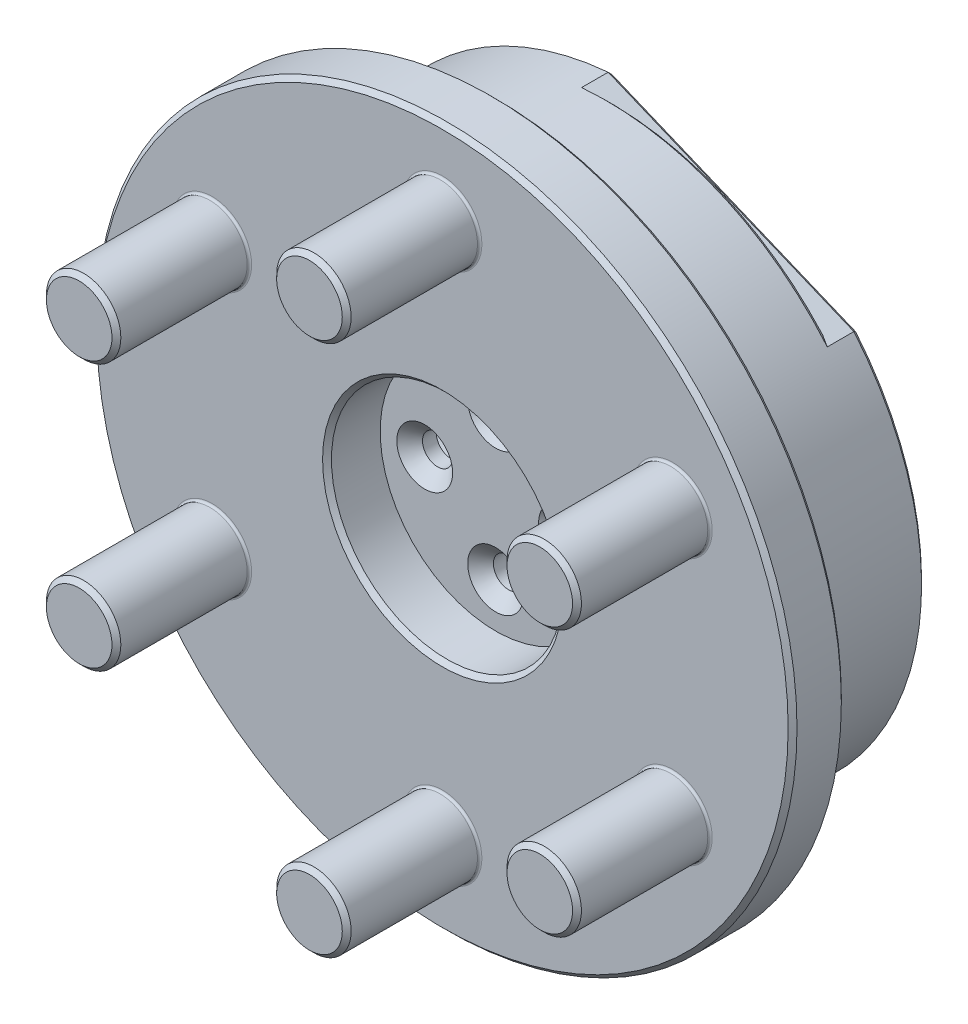
SolidWorks part; units mm, degrees
material "7075-T6, Plate (SS)"
ref_plane "Front Plane" through (0, 0, 0) normal (0, 0, 1) x (1, 0, 0)
ref_plane "Top Plane" through (0, 0, 0) normal (0, 1, 0) x (1, 0, 0)
ref_plane "Right Plane" through (0, 0, 0) normal (1, 0, 0) x (0, 0, -1)
sketch "Sketch1" plane through (0, 0, 0) normal (0, 0, 1) x (1, 0, 0)
  circle A0 centre (0, 0) radius 39.5
  circle A1 centre (0, 30) radius 4.2
  circle A2 centre (0, 0) radius 13.025
  circle A3 centre (25.9808, 15) radius 4.2
  circle A4 centre (25.9808, -15) radius 4.2
  circle A5 centre (0, -30) radius 4.2
  circle A6 centre (-25.9808, -15) radius 4.2
  circle A7 centre (-25.9808, 15) radius 4.2
  point P18 (0, 0)
  dimension "D1" = 79
  dimension "D3" = 8.4
  dimension "D4" = 26.05
  dimension "D2" = 30
  dimension "D5" = 6
extrude "Boss-Extrude1" add sketch "Sketch1" against normal blind 6 contours A0 | A2
extrude "Boss-Extrude2" add sketch "Sketch1<3>" along normal blind 15 contours A3 | A4 | A5 | A6 | A7 | A1 region at (25.9808, 15, 0) region at (25.9808, -15, 0) region at (0, -30, 0) region at (-25.9808, -15, 0) region at (-25.9808, 15, 0)
sketch "Sketch1<3>" plane through (0, 0, 0) normal (0, 0, 1) x (1, 0, 0) same geometry as "Sketch1"
sketch "Sketch2" plane through (0, 0, -6) normal (0, 0, -1) x (-1, 0, 0)
  circle A0 centre (0, 0) radius 32.55
  circle A1 centre (0, 0) radius 17.5
  circle A4 centre (0, 0) radius 25 construction
  point P18 (0, 0)
  dimension "D1" = 65.1
  dimension "D2" = 50
  dimension "D3" = 35
extrude "Boss-Extrude3" add sketch "Sketch2" along normal blind 16 contours A0
sketch "Sketch3" plane through (0, 0, -22) normal (0, 0, -1) x (-1, 0, 0)
  circle A0 centre (0, 0) radius 25 construction
  point P3 (0, 25)
  point P7 (17.6777, 17.6777)
  point P8 (25, 0)
  point P9 (17.6777, -17.6777)
  point P10 (0, -25)
  point P11 (-17.6777, -17.6777)
  point P12 (-25, 0)
  point P13 (-17.6777, 17.6777)
  point P14 (0, 0)
  point P17 (0, 0)
  dimension "D1" = 50
  dimension "D2" = 8
sketch "Sketch5" plane through (0, 0, 0) normal (0, 0, 1) x (1, 0, 0)
  circle A0 centre (0, 30) radius 4
  circle A1 centre (25.9808, 15) radius 4
  circle A2 centre (25.9808, -15) radius 4
  circle A3 centre (0, -30) radius 4
  circle A4 centre (-25.9808, -15) radius 4
  circle A5 centre (-25.9808, 15) radius 4
  point P15 (0, 0)
  dimension "D2" = 8
  dimension "D1" = 30
  dimension "D3" = 6
extrude "Boss-Extrude4" [suppressed] add sketch "Sketch5" along normal blind 15
fillet "Fillet1" [suppressed] radius 0.5
hole_wizard "M5 Tapped Hole1" positions "Sketch6" profile "Sketch7" tap size "M5" standard "ISO"
sketch "Sketch6" plane through (0, 0, -22) normal (0, 0, -1) x (-1, 0, 0)
  point P0 (0, 25)
  point P3 (-17.6777, 17.6777)
  point P6 (-25, 0)
  point P9 (17.6777, 17.6777)
  point P12 (25, 0)
  point P15 (-17.6777, -17.6777)
  point P18 (0, -25)
  point P21 (17.6777, -17.6777)
sketch "Sketch7" plane through (0, 25, -22) normal (1, 0, 0) x (0, 1, 0)
  line L0 (0, 0) -> (0, 8.2618)
  line L1 (0, 8.2618) -> (2.1, 7)
  line L2 (2.1, 7) -> (2.1, 0.425)
  line L3 (2.1, 0.425) -> (2.525, 0)
  line L5 (2.525, 0) -> (0, 0)
  line L6 (-2.1, 0.425) -> (-2.525, 0) construction
  line L10 (0, 8.2618) -> (-2.1, 7) construction
  line L11 (0, -6.35) -> (0, 107.95) construction
  dimension "Tap Drill Dia." = 4.2
  dimension "Tap Drill Depth" = 7
  dimension "Near C'Sink Dia." = 5.05
  dimension "Near C'Sink Angle" = 90
  dimension "Drill Angle" = 118
sketch "Sketch9" plane through (0, 0, -22) normal (0, 0, -1) x (-1, 0, 0)
  line L0 (0, 0) -> (-12.4563, 30.0723) construction
  line L1 (-24.9131, 20.9486) -> (2.8033, 32.4291)
  line L2 (0, 0) -> (0, 32.55) construction
  line L3 (24.9131, -20.9486) -> (-2.8033, -32.4291)
  circle A0 centre (0, 0) radius 32.55 construction
  arc A1 (2.8033, 32.4291) -> (-24.9131, 20.9486) centre (0, 0) ccw
  arc A2 (-12.9309, 13.2303) -> (-13.2303, 12.9309) centre (0, 0) ccw
  arc A3 (-2.8033, -32.4291) -> (24.9131, -20.9486) centre (0, 0) ccw
  circle A4 centre (0, 0) radius 25 construction
  arc A5 (-3.0239, 20.3657) -> (-12.2625, 16.5389) centre (-7.6537, 18.4776) ccw
  arc A6 (12.2625, 16.5389) -> (3.0239, 20.3657) centre (7.6537, 18.4776) ccw
  arc A7 (20.3657, 3.0239) -> (16.5389, 12.2625) centre (18.4776, 7.6537) ccw
  arc A8 (16.5389, -12.2625) -> (20.3657, -3.0239) centre (18.4776, -7.6537) ccw
  arc A9 (3.0239, -20.3657) -> (12.2625, -16.5389) centre (7.6537, -18.4776) ccw
  arc A10 (-12.2625, -16.5389) -> (-3.0239, -20.3657) centre (-7.6537, -18.4776) ccw
  arc A11 (-20.3657, -3.0239) -> (-16.5389, -12.2625) centre (-18.4776, -7.6537) ccw
  arc A12 (-16.5389, 12.2625) -> (-20.3657, 3.0239) centre (-18.4776, 7.6537) ccw
  arc A13 (0.2117, 18.4988) -> (-0.2117, 18.4988) centre (0, 0) ccw
  arc A14 (13.2303, 12.9309) -> (12.9309, 13.2303) centre (0, 0) ccw
  arc A15 (18.4988, -0.2117) -> (18.4988, 0.2117) centre (0, 0) ccw
  arc A16 (12.9309, -13.2303) -> (13.2303, -12.9309) centre (0, 0) ccw
  arc A17 (-0.2117, -18.4988) -> (0.2117, -18.4988) centre (0, 0) ccw
  arc A18 (-13.2303, -12.9309) -> (-12.9309, -13.2303) centre (0, 0) ccw
  arc A19 (-18.4988, 0.2117) -> (-18.4988, -0.2117) centre (0, 0) ccw
  arc A20 (-16.5389, 12.2625) -> (-13.2303, 12.9309) centre (-15.3757, 15.0279) ccw
  arc A21 (-12.9309, 13.2303) -> (-12.2625, 16.5389) centre (-15.0279, 15.3757) ccw
  arc A22 (-20.3657, 3.0239) -> (-18.4988, 0.2117) centre (-21.4986, 0.246) cw
  arc A23 (-20.3657, -3.0239) -> (-18.4988, -0.2117) centre (-21.4986, -0.246) ccw
  arc A24 (-16.5389, -12.2625) -> (-13.2303, -12.9309) centre (-15.3757, -15.0279) cw
  arc A25 (-12.2625, -16.5389) -> (-12.9309, -13.2303) centre (-15.0279, -15.3757) ccw
  arc A26 (-3.0239, -20.3657) -> (-0.2117, -18.4988) centre (-0.246, -21.4986) cw
  arc A27 (3.0239, -20.3657) -> (0.2117, -18.4988) centre (0.246, -21.4986) ccw
  arc A28 (12.2625, -16.5389) -> (12.9309, -13.2303) centre (15.0279, -15.3757) cw
  arc A29 (16.5389, -12.2625) -> (13.2303, -12.9309) centre (15.3757, -15.0279) ccw
  arc A30 (18.4988, 0.2117) -> (20.3657, 3.0239) centre (21.4986, 0.246) cw
  arc A31 (20.3657, -3.0239) -> (18.4988, -0.2117) centre (21.4986, -0.246) cw
  arc A32 (13.2303, 12.9309) -> (16.5389, 12.2625) centre (15.3757, 15.0279) ccw
  arc A33 (12.9309, 13.2303) -> (12.2625, 16.5389) centre (15.0279, 15.3757) cw
  arc A34 (0.2117, 18.4988) -> (3.0239, 20.3657) centre (0.246, 21.4986) ccw
  arc A35 (-0.2117, 18.4988) -> (-3.0239, 20.3657) centre (-0.246, 21.4986) cw
  point P13 (0, 0)
  point P31 (0, 0)
  point P42 (-18.3083, 2.6565)
  point P47 (-14.8244, -11.0674)
  point P52 (-2.6565, -18.3083)
  point P57 (11.0674, -14.8244)
  point P64 (18.3083, -2.6565)
  dimension "D1" = 37
  dimension "D7" = 3
  dimension "D8" = 3
  dimension "D2" = 22.5
  dimension "D3" = 30
  dimension "D5" = 20
  dimension "D4" = 2
  dimension "D6" = 8
extrude "Cut-Extrude1" cut sketch "Sketch9" against normal blind 12 contours A2 A20 A12 A22 A19 A23 A11 A24 A18 A25 A10 A26 A17 A27 A9 A28 A16 A29 A8 A31 A15 A30 A7 A32 A14 A33 A6 A34 A13 A35 A5 A21
sketch "Sketch10" plane through (0, 0, -22) normal (0, 0, -1) x (-1, 0, 0)
  line L1 (24.9131, -20.9486) -> (-2.8033, -32.4291)
  line L2 (24.9131, -20.9486) -> (-2.8033, -32.4291)
  line L3 (-24.9131, 20.9486) -> (2.8033, 32.4291)
  line L4 (-24.9131, 20.9486) -> (2.8033, 32.4291)
  arc A3 (-2.8033, -32.4291) -> (24.9131, -20.9486) centre (0, 0) ccw
  arc A4 (-2.8033, -32.4291) -> (24.9131, -20.9486) centre (0, 0) ccw
  arc A5 (2.8033, 32.4291) -> (-24.9131, 20.9486) centre (0, 0) ccw
  arc A6 (2.8033, 32.4291) -> (-24.9131, 20.9486) centre (0, 0) ccw
  dimension "D2" = 0
  dimension "D3" = 0
extrude "Cut-Extrude2" cut sketch "Sketch10" against normal blind 3
fillet "Fillet2" radius 0.25 6 edges at (4.2, -30, 0) (30.1808, -15, 0) (-21.7808, -15, 0) (30.1808, 15, 0) (-21.7808, 15, 0) (4.2, 30, 0)
chamfer "Chamfer1" distance 0.5 angle 45 6 edges at (30.1808, -15, 15) (4.2, -30, 15) (-21.7808, -15, 15) (30.1808, 15, 15) (4.2, 30, 15) (-21.7808, 15, 15)
chamfer "Chamfer2" distance 0.5 angle 45 40 edges at (13.0815, 13.0815, -22) (-12.4563, -30.0723, -19) (13.025, 0, 0) (12.4563, 30.0723, -19) (30.0723, -12.4563, -22) (11.0549, 26.6888, -22) (-30.0723, 12.4563, -22) (39.5, 0, -6) (39.5, 0, 0) (-13.0815, -13.0815, -22) (-14.7817, -12.0873, -22) (-12.0873, -14.7817, -22) (-23.097, -9.5671, -22) (-9.5671, -23.097, -22) (-18.9992, -1.9053, -22) (-1.9053, -18.9992, -22) (-18.5, 0, -22) (0, -18.5, -22) (-18.9992, 1.9053, -22) (1.9053, -18.9992, -22) (-23.097, 9.5671, -22) (9.5671, -23.097, -22) (-14.7817, 12.0873, -22) (12.0873, -14.7817, -22) (-13.0815, 13.0815, -22) (13.0815, -13.0815, -22) (-12.0873, 14.7817, -22) (14.7817, -12.0873, -22) (-9.5671, 23.097, -22) (23.097, -9.5671, -22) (-1.9053, 18.9992, -22) (18.9992, -1.9053, -22) (0, 18.5, -22) (18.5, 0, -22) (1.9053, 18.9992, -22) (18.9992, 1.9053, -22) (9.5671, 23.097, -22) (23.097, 9.5671, -22) (12.0873, 14.7817, -22) (14.7817, 12.0873, -22)
sketch "Sketch11" plane through (0, 0, -10) normal (0, 0, -1) x (-1, 0, 0)
  circle A0 centre (0, 0) radius 11.05
  circle A1 centre (0, 0) radius 8 construction
  dimension "D1" = 22.1
  dimension "D2" = 16
extrude "Cut-Extrude3" cut sketch "Sketch11" against normal blind 1
chamfer "Chamfer3" distance 0.25 angle 45 1 edges at (-11.05, 0, -10)
sketch "Sketch12" plane through (0, 0, -9) normal (0, 0, -1) x (-1, 0, 0)
  circle A0 centre (0, 0) radius 8 construction
  point P3 (0, 8)
  point P4 (-8, 0)
  point P5 (0, -8)
  point P6 (8, 0)
  dimension "D1" = 16
sketch "Sketch15" plane through (0, 0, -10) normal (0, 0, -1) x (-1, 0, 0)
  circle A0 centre (0, 0) radius 12.5
  arc A32 (-12.9309, 13.2303) -> (-12.2625, 16.5389) centre (-15.0279, 15.3757) ccw
  arc A33 (-12.9309, 13.2303) -> (-13.2303, 12.9309) centre (0, 0) ccw
  arc A34 (-16.5389, 12.2625) -> (-13.2303, 12.9309) centre (-15.3757, 15.0279) ccw
  arc A35 (-16.5389, 12.2625) -> (-20.3657, 3.0239) centre (-18.4776, 7.6537) ccw
  arc A36 (-18.4988, 0.2117) -> (-20.3657, 3.0239) centre (-21.4986, 0.246) ccw
  arc A37 (-18.4988, 0.2117) -> (-18.4988, -0.2117) centre (0, 0) ccw
  arc A38 (-20.3657, -3.0239) -> (-18.4988, -0.2117) centre (-21.4986, -0.246) ccw
  arc A39 (-20.3657, -3.0239) -> (-16.5389, -12.2625) centre (-18.4776, -7.6537) ccw
  arc A40 (-13.2303, -12.9309) -> (-16.5389, -12.2625) centre (-15.3757, -15.0279) ccw
  arc A41 (-13.2303, -12.9309) -> (-12.9309, -13.2303) centre (0, 0) ccw
  arc A42 (-12.2625, -16.5389) -> (-12.9309, -13.2303) centre (-15.0279, -15.3757) ccw
  arc A43 (-12.2625, -16.5389) -> (-3.0239, -20.3657) centre (-7.6537, -18.4776) ccw
  arc A44 (-0.2117, -18.4988) -> (-3.0239, -20.3657) centre (-0.246, -21.4986) ccw
  arc A45 (-0.2117, -18.4988) -> (0.2117, -18.4988) centre (0, 0) ccw
  arc A46 (3.0239, -20.3657) -> (0.2117, -18.4988) centre (0.246, -21.4986) ccw
  arc A47 (3.0239, -20.3657) -> (12.2625, -16.5389) centre (7.6537, -18.4776) ccw
  arc A48 (12.9309, -13.2303) -> (12.2625, -16.5389) centre (15.0279, -15.3757) ccw
  arc A49 (12.9309, -13.2303) -> (13.2303, -12.9309) centre (0, 0) ccw
  arc A50 (16.5389, -12.2625) -> (13.2303, -12.9309) centre (15.3757, -15.0279) ccw
  arc A51 (16.5389, -12.2625) -> (20.3657, -3.0239) centre (18.4776, -7.6537) ccw
  arc A52 (18.4988, -0.2117) -> (20.3657, -3.0239) centre (21.4986, -0.246) ccw
  arc A53 (18.4988, -0.2117) -> (18.4988, 0.2117) centre (0, 0) ccw
  arc A54 (20.3657, 3.0239) -> (18.4988, 0.2117) centre (21.4986, 0.246) ccw
  arc A55 (20.3657, 3.0239) -> (16.5389, 12.2625) centre (18.4776, 7.6537) ccw
  arc A56 (13.2303, 12.9309) -> (16.5389, 12.2625) centre (15.3757, 15.0279) ccw
  arc A57 (13.2303, 12.9309) -> (12.9309, 13.2303) centre (0, 0) ccw
  arc A58 (12.2625, 16.5389) -> (12.9309, 13.2303) centre (15.0279, 15.3757) ccw
  arc A59 (12.2625, 16.5389) -> (3.0239, 20.3657) centre (7.6537, 18.4776) ccw
  arc A60 (0.2117, 18.4988) -> (3.0239, 20.3657) centre (0.246, 21.4986) ccw
  arc A61 (0.2117, 18.4988) -> (-0.2117, 18.4988) centre (0, 0) ccw
  arc A62 (-3.0239, 20.3657) -> (-0.2117, 18.4988) centre (-0.246, 21.4986) ccw
  arc A63 (-3.0239, 20.3657) -> (-12.2625, 16.5389) centre (-7.6537, 18.4776) ccw
  arc A64 (-12.9309, 13.2303) -> (-12.2625, 16.5389) centre (-15.0279, 15.3757) ccw
  arc A65 (-12.9309, 13.2303) -> (-13.2303, 12.9309) centre (0, 0) ccw
  arc A66 (-16.5389, 12.2625) -> (-13.2303, 12.9309) centre (-15.3757, 15.0279) ccw
  arc A67 (-16.5389, 12.2625) -> (-20.3657, 3.0239) centre (-18.4776, 7.6537) ccw
  arc A68 (-18.4988, 0.2117) -> (-20.3657, 3.0239) centre (-21.4986, 0.246) ccw
  arc A69 (-18.4988, 0.2117) -> (-18.4988, -0.2117) centre (0, 0) ccw
  arc A70 (-20.3657, -3.0239) -> (-18.4988, -0.2117) centre (-21.4986, -0.246) ccw
  arc A71 (-20.3657, -3.0239) -> (-16.5389, -12.2625) centre (-18.4776, -7.6537) ccw
  arc A72 (-13.2303, -12.9309) -> (-16.5389, -12.2625) centre (-15.3757, -15.0279) ccw
  arc A73 (-13.2303, -12.9309) -> (-12.9309, -13.2303) centre (0, 0) ccw
  arc A74 (-12.2625, -16.5389) -> (-12.9309, -13.2303) centre (-15.0279, -15.3757) ccw
  arc A75 (-12.2625, -16.5389) -> (-3.0239, -20.3657) centre (-7.6537, -18.4776) ccw
  arc A76 (-0.2117, -18.4988) -> (-3.0239, -20.3657) centre (-0.246, -21.4986) ccw
  arc A77 (-0.2117, -18.4988) -> (0.2117, -18.4988) centre (0, 0) ccw
  arc A78 (3.0239, -20.3657) -> (0.2117, -18.4988) centre (0.246, -21.4986) ccw
  arc A79 (3.0239, -20.3657) -> (12.2625, -16.5389) centre (7.6537, -18.4776) ccw
  arc A80 (12.9309, -13.2303) -> (12.2625, -16.5389) centre (15.0279, -15.3757) ccw
  arc A81 (12.9309, -13.2303) -> (13.2303, -12.9309) centre (0, 0) ccw
  arc A82 (16.5389, -12.2625) -> (13.2303, -12.9309) centre (15.3757, -15.0279) ccw
  arc A83 (16.5389, -12.2625) -> (20.3657, -3.0239) centre (18.4776, -7.6537) ccw
  arc A84 (18.4988, -0.2117) -> (20.3657, -3.0239) centre (21.4986, -0.246) ccw
  arc A85 (18.4988, -0.2117) -> (18.4988, 0.2117) centre (0, 0) ccw
  arc A86 (20.3657, 3.0239) -> (18.4988, 0.2117) centre (21.4986, 0.246) ccw
  arc A87 (20.3657, 3.0239) -> (16.5389, 12.2625) centre (18.4776, 7.6537) ccw
  arc A88 (13.2303, 12.9309) -> (16.5389, 12.2625) centre (15.3757, 15.0279) ccw
  arc A89 (13.2303, 12.9309) -> (12.9309, 13.2303) centre (0, 0) ccw
  arc A90 (12.2625, 16.5389) -> (12.9309, 13.2303) centre (15.0279, 15.3757) ccw
  arc A91 (12.2625, 16.5389) -> (3.0239, 20.3657) centre (7.6537, 18.4776) ccw
  arc A92 (0.2117, 18.4988) -> (3.0239, 20.3657) centre (0.246, 21.4986) ccw
  arc A93 (0.2117, 18.4988) -> (-0.2117, 18.4988) centre (0, 0) ccw
  arc A94 (-3.0239, 20.3657) -> (-0.2117, 18.4988) centre (-0.246, 21.4986) ccw
  arc A95 (-3.0239, 20.3657) -> (-12.2625, 16.5389) centre (-7.6537, 18.4776) ccw
  dimension "D2" = 25
  dimension "D1" = 0
sketch "Sketch16" plane through (0, 0, -6) normal (0, 0, 1) x (1, 0, 0)
  point P0 (0, 8)
  point P1 (-8, 0)
  point P3 (0, -8)
  point P5 (8, 0)
hole_wizard "CSK for M3 Countersunk Flat Head Screw1" positions "Sketch17" profile "Sketch18" countersink size "M3" standard "ISO" end condition through all
sketch "Sketch17" plane through (0, 0, -6) normal (0, 0, 1) x (1, 0, 0)
  point P0 (0, 8)
  point P3 (-8, 0)
  point P6 (0, -8)
  point P9 (8, 0)
sketch "Sketch18" plane through (0, 8, -6) normal (1, 0, 0) x (0, -1, 0)
  line L0 (0, 0) -> (0, 16)
  line L1 (0, 16) -> (1.7, 16)
  line L2 (1.7, 16) -> (1.7, 1.45)
  line L3 (1.7, 1.45) -> (3.15, 0)
  line L5 (3.15, 0) -> (0, 0)
  line L6 (-1.7, 1.45) -> (-3.15, 0) construction
  line L11 (0, -6.35) -> (0, 107.95) construction
  dimension "Thru Hole Dia." = 3.4
  dimension "Thru Hole Depth" = 16
  dimension "Near C'Sink Dia." = 6.3
  dimension "Near C'Sink Angle" = 90
